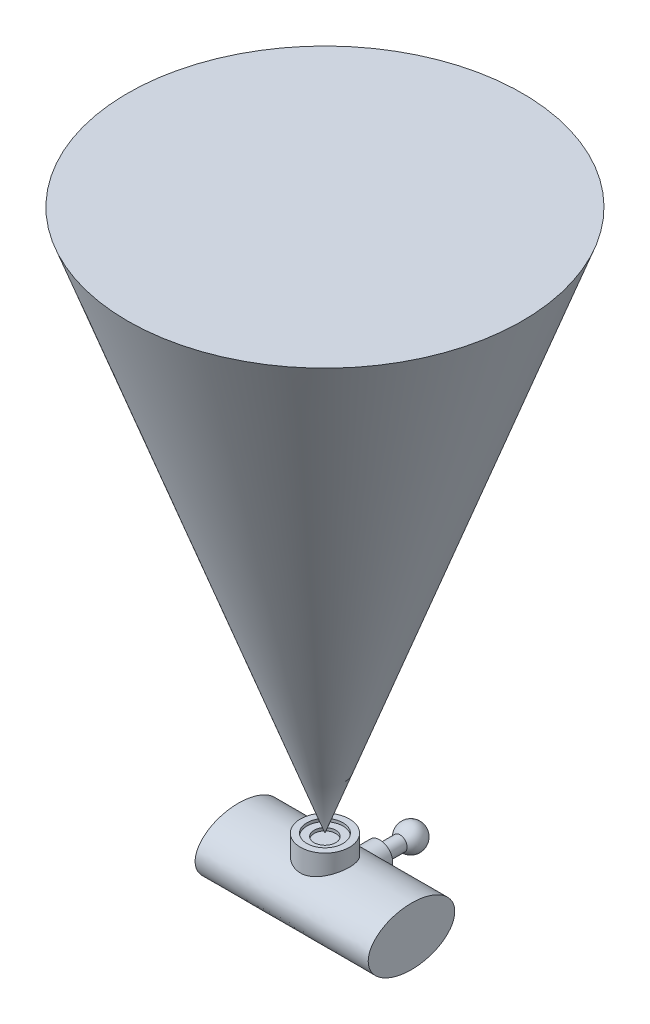
SolidWorks part; units mm, degrees
ref_plane "前视基准面" through (0, 0, 0) normal (0, 0, 1) x (1, 0, 0)
ref_plane "上视基准面" through (0, 0, 0) normal (0, 1, 0) x (1, 0, 0)
ref_plane "右视基准面" through (0, 0, 0) normal (1, 0, 0) x (0, 0, -1)
ref_axis "基准轴1" through (0, 0, -10.7037) along (0, 0, 1)
sketch "草图1" plane through (0, 0, 0) normal (0, 0, 1) x (1, 0, 0)
  circle A0 centre (0, 0) radius 2.5
  dimension "D1" = 5
extrude "凸台-拉伸1" add sketch "草图1" along normal blind 7
sketch "草图2" plane through (0, 0, 7) normal (0, 0, 1) x (1, 0, 0)
  circle A0 centre (0, 0) radius 4.5
  dimension "D1" = 9
extrude "凸台-拉伸2" add sketch "草图2" along normal blind 10
sketch "草图3" plane through (0, 0, 0) normal (1, 0, 0) x (0, 0, -1)
  ellipse E0 centre (-26, 0) end of major axis (-11, 0) minor radius 10
  dimension "D1" = 26
extrude "凸台-拉伸3" add sketch "草图3" along normal blind 30 and the other way blind 30 contours E0
sketch "草图4" plane through (0, 0, 0) normal (0, 1, 0) x (1, 0, 0)
  line L0 (2.5, 0) -> (-2.5, 0) construction
  circle A0 centre (0, -26) radius 8.5
  dimension "D1" = 26
  dimension "D2" = 17
extrude "凸台-拉伸4" add sketch "草图4" along normal blind 16
sketch "草图5" plane through (0, 16, 0) normal (0, 1, 0) x (1, 0, 0)
  circle A0 centre (0, -26) radius 6.25
  dimension "D1" = 12.5
extrude "切除-拉伸1" cut sketch "草图5" against normal blind 1
sketch "草图6" plane through (0, 15, 0) normal (0, 1, 0) x (1, 0, 0)
  circle A0 centre (0, -26) radius 3.75
  dimension "D1" = 7.5
extrude "切除-拉伸2" cut sketch "草图6" against normal blind 1
sketch "草图7" plane through (0, 0, 0) normal (0, 1, 0) x (1, 0, 0)
  line L1 (0, -0.7583) -> (0, 8.2417)
  arc A1 (0, -0.7583) -> (0, 8.2417) centre (0, 3.7417) ccw
revolve "旋转3" add sketch "草图7" angle 360 about axis through (0, 0, -10.7037) along (0, 0, 1)
sketch "草图8" plane through (0, 0, 0) normal (1, 0, 0) x (0, 0, -1)
  line L0 (-26, 16) -> (42.404, 203.9385)
  line L1 (-19.75, 16) -> (-32.25, 16) construction
  line L2 (42.404, 203.9385) -> (-26, 203.9385)
  line L3 (-26, 203.9385) -> (-26, 16)
revolve "旋转4" add sketch "草图8" angle 360 about L3
